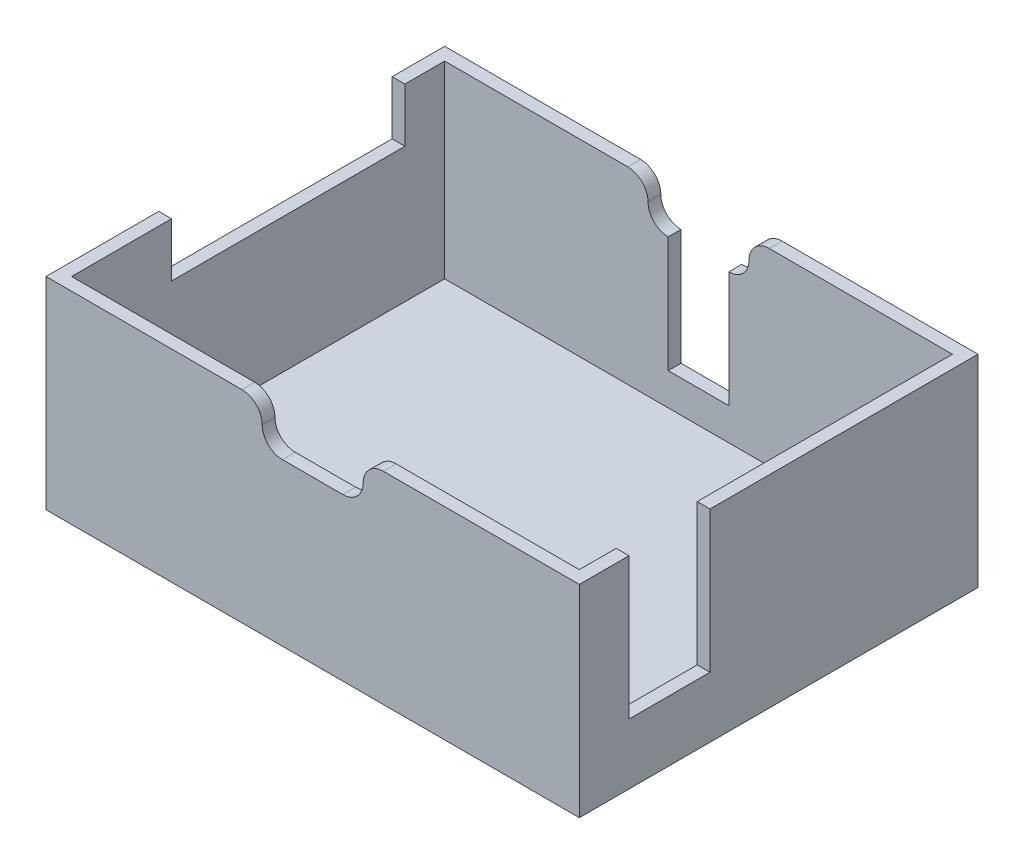
SolidWorks part; units mm, degrees
ref_plane "Front Plane" through (0, 0, 0) normal (0, 0, 1) x (1, 0, 0)
ref_plane "Top Plane" through (0, 0, 0) normal (0, 1, 0) x (1, 0, 0)
ref_plane "Right Plane" through (0, 0, 0) normal (1, 0, 0) x (0, 0, -1)
sketch "Sketch1" plane through (0, 0, 0) normal (0, 1, 0) x (1, 0, 0)
  line L1 (0, 0) -> (100.584, 0)
  line L2 (0, 0) -> (0, 75.184)
  line L3 (0, 75.184) -> (100.584, 75.184)
  line L4 (100.584, 0) -> (100.584, 75.184)
  dimension "D1" = 75.184
  dimension "D2" = 100.584
extrude "Boss-Extrude1" add sketch "Sketch1" along normal blind 2.54
sketch "Sketch2" plane through (0, 2.54, 0) normal (0, 1, 0) x (1, 0, 0)
  line L1 (0, 75.184) -> (100.584, 75.184)
  line L2 (0, 75.184) -> (0, 0)
  line L3 (0, 0) -> (100.584, 0)
  line L4 (100.584, 75.184) -> (100.584, 0)
  line L5 (2.413, 72.771) -> (98.171, 72.771)
  line L6 (2.413, 72.771) -> (2.413, 2.413)
  line L7 (2.413, 2.413) -> (98.171, 2.413)
  line L8 (98.171, 72.771) -> (98.171, 2.413)
  point P10 (0, 37.592)
  point P11 (50.292, 75.184)
  point P12 (50.292, 72.771)
  point P14 (2.413, 37.592)
  dimension "D1" = 70.358
  dimension "D2" = 95.758
extrude "Boss-Extrude2" add sketch "Sketch2" along normal blind 35.56
sketch "Sketch3" plane through (0, 0, -75.184) normal (0, 0, -1) x (-1, 0, 0)
  line L0 (-100.584, 38.1) -> (0, 38.1) construction
  line L1 (-59.817, 38.1) -> (-40.767, 38.1)
  line L2 (-59.817, 38.1) -> (-59.817, 30.48)
  line L3 (-59.817, 30.48) -> (-40.767, 30.48)
  line L4 (-40.767, 38.1) -> (-40.767, 30.48)
  line L5 (-100.584, 0) -> (0, 0) construction
  point P6 (-50.292, 30.48)
  point P7 (-50.292, 0)
  dimension "D1" = 19.05
  dimension "D2" = 7.62
extrude "Cut-Extrude1" cut sketch "Sketch3" against normal through all
fillet "Fillet1" radius 3.81 8 edges at (40.767, 30.48, -1.2065) (59.817, 30.48, -1.2065) (59.817, 30.48, -73.9775) (40.767, 30.48, -73.9775) (40.767, 38.1, -1.2065) (59.817, 38.1, -1.2065) (59.817, 38.1, -73.9775) (40.767, 38.1, -73.9775)
sketch "Sketch4" plane through (0, 0, 0) normal (-1, 0, 0) x (0, 0, 1)
  line L0 (-75.184, 38.1) -> (0, 38.1) construction
  line L1 (-58.928, 38.1) -> (-65.278, 38.1)
  line L3 (-58.928, 27.9403) -> (-65.278, 27.9403)
  line L4 (-65.278, 31.7503) -> (-65.278, 27.9403)
  line L6 (-65.278, 31.7503) -> (-65.278, 38.1)
  line L8 (-58.928, 27.9403) -> (-21.2707, 27.9403)
  line L9 (-21.2707, 27.9403) -> (-21.2707, 38.1)
  line L10 (-21.2707, 38.1) -> (-58.928, 38.1)
extrude "Cut-Extrude2" cut sketch "Sketch4" against normal blind 6.35 contours L4 L3 L8 region at (0, 33.0201, -43.2744)
sketch "Sketch5" plane through (100.584, 0, 0) normal (1, 0, 0) x (0, 0, -1)
  line L1 (24.638, 11.4303) -> (9.3593, 11.4303)
  line L2 (24.638, 11.4303) -> (24.638, 38.1003)
  line L3 (24.638, 38.1003) -> (9.3593, 38.1003)
  line L4 (9.3593, 11.4303) -> (9.3593, 38.1003)
extrude "Cut-Extrude3" cut sketch "Sketch5" against normal blind 6.35 contours L2 L3 L4 L1
sketch "Sketch6" plane through (0, 0, -75.184) normal (0, 0, -1) x (-1, 0, 0)
  line L1 (-44.577, 30.48) -> (-56.007, 30.48)
  line L2 (-44.577, 30.48) -> (-44.577, 8.6209)
  line L3 (-44.577, 8.6209) -> (-56.007, 8.6209)
  line L4 (-56.007, 30.48) -> (-56.007, 8.6209)
  point P5 (-52.2079, 30.48)
extrude "Cut-Extrude4" cut sketch "Sketch6" against normal blind 6.35
